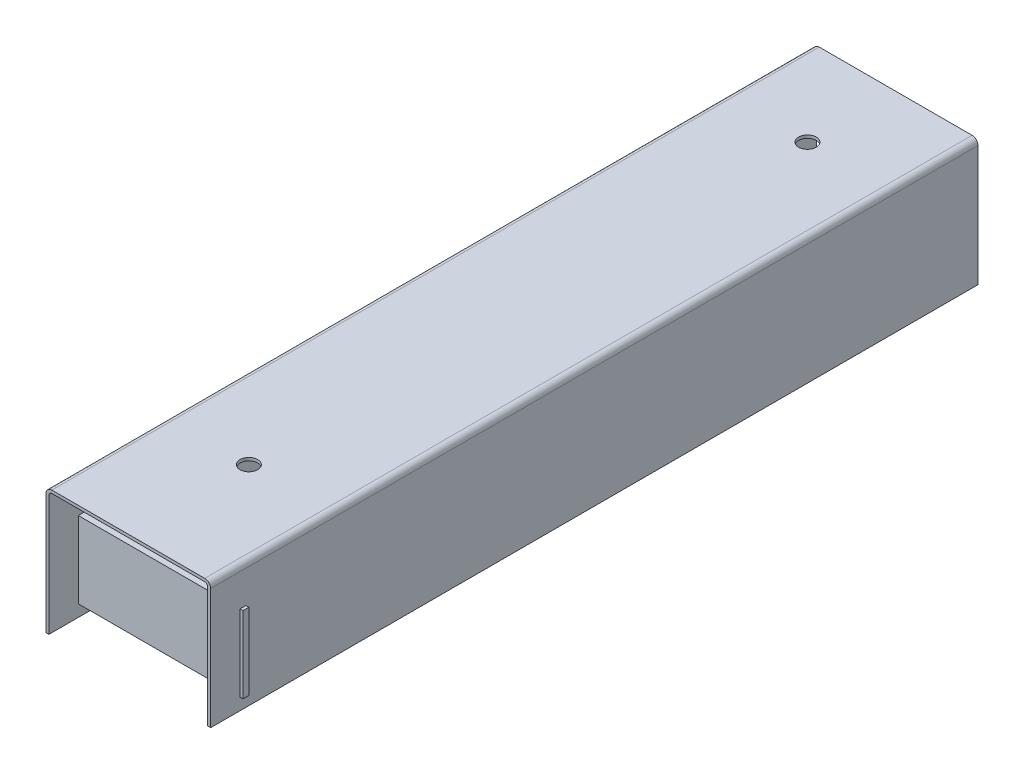
SolidWorks part; units mm, degrees
ref_plane "Płaszczyzna przednia" through (0, 0, 0) normal (0, 0, 1) x (1, 0, 0)
ref_plane "Płaszczyzna górna" through (0, 0, 0) normal (0, 1, 0) x (1, 0, 0)
ref_plane "Płaszczyzna prawa" through (0, 0, 0) normal (1, 0, 0) x (0, 0, -1)
sketch "Sketch1" plane through (0, 0, 0) normal (0, 0, 1) x (1, 0, 0)
  line L0 (26.6977, -20.5) -> (27, -20.5)
  line L1 (-28, 21.5) -> (28, 21.5)
  line L2 (-28, 21.5) -> (-28, -21.5)
  line L4 (28, 21.5) -> (28, -21.5)
  line L5 (-28, 21.5) -> (28, -21.5) construction
  line L6 (-28, -21.5) -> (28, 21.5) construction
  line L7 (-27, 20.5) -> (27, 20.5)
  line L8 (-27, 20.5) -> (-27, -20.5)
  line L9 (-27, -20.5) -> (-26.6977, -20.5)
  line L10 (27, 20.5) -> (27, -20.5)
  line L11 (-27, 20.5) -> (27, -20.5) construction
  line L12 (-27, -20.5) -> (27, 20.5) construction
  line L13 (-28, -21.5) -> (-27, -21.5)
  line L14 (-27, -21.5) -> (-27, -20.5)
  line L15 (28, -21.5) -> (27, -21.5)
  line L16 (27, -21.5) -> (27, -20.5)
  point P0 (0, 0)
  point P6 (0, 0)
  dimension "D1" = 56
  dimension "D2" = 43
  dimension "D3" = 54
  dimension "D4" = 41
extrude "Boss-Extrude1" add sketch "Sketch1" along normal blind 261 contours L16 L15 L4 L1 L2 L13 L14 L8 L7 L10 region at (0, 20.794, 0)
fillet "Fillet1" radius 2 2 edges at (-28, 21.5, 130.5) (28, 21.5, 130.5)
fillet "Fillet2" radius 1 2 edges at (27, 20.5, 130.5) (-27, 20.5, 130.5)
sketch "Sketch2" plane through (-27, 0, 0) normal (1, 0, 0) x (0, 0, -1)
  line L0 (-251, -21.5) -> (-251, 19.5) construction
  line L1 (-261, -21.5) -> (0, -21.5) construction
  line L2 (0, 19.5) -> (-261, 19.5) construction
  line L3 (-261, 19.5) -> (-261, -21.5) construction
  line L4 (-251, -17.5) -> (-261, -17.5) construction
  line L10 (-251, -17.5) -> (-249, -17.5)
  line L11 (-251, -17.5) -> (-251, 8.5)
  line L12 (-251, 8.5) -> (-249, 8.5)
  line L13 (-249, -17.5) -> (-249, 8.5)
  line L14 (-251, -17.5) -> (-249, 8.5) construction
  line L15 (-251, 8.5) -> (-249, -17.5) construction
  point P14 (-250, -4.5)
  dimension "D1" = 10
  dimension "D2" = 4
  dimension "D3" = 2
  dimension "D4" = 26
extrude "Boss-Extrude2" add sketch "Sketch2" along normal blind 56 and the other way blind 2
sketch "Sketch3" plane through (0, 21.5, 0) normal (0, 1, 0) x (1, 0, 0)
  line L0 (0, 0) -> (0, -261) construction
  line L1 (-26, 0) -> (26, 0) construction
  line L2 (-26, -261) -> (26, -261) construction
  circle A0 centre (0, -30) radius 3
  circle A1 centre (0, -220) radius 3
  dimension "D1" = 30
  dimension "D2" = 41
extrude "Cut-Extrude1" cut sketch "Sketch3" against normal blind 11
sketch "Sketch4" plane through (-28, 0, 0) normal (-1, 0, 0) x (0, 0, 1)
  line L0 (0, 21.5) -> (261, 21.5) construction
  line L1 (206, 16.5) -> (236, 16.5)
  line L2 (206, 16.5) -> (206, -23.5)
  line L3 (206, -23.5) -> (236, -23.5)
  line L4 (236, 16.5) -> (236, -23.5)
  line L5 (206, 16.5) -> (236, -23.5) construction
  line L6 (206, -23.5) -> (236, 16.5) construction
  line L7 (261, 19.5) -> (261, -21.5) construction
  point P4 (221, -3.5)
  dimension "D1" = 5
  dimension "D2" = 25
  dimension "D3" = 30
  dimension "D4" = 40
extrude "Cut-Extrude2" cut sketch "Sketch4" against normal blind 10
